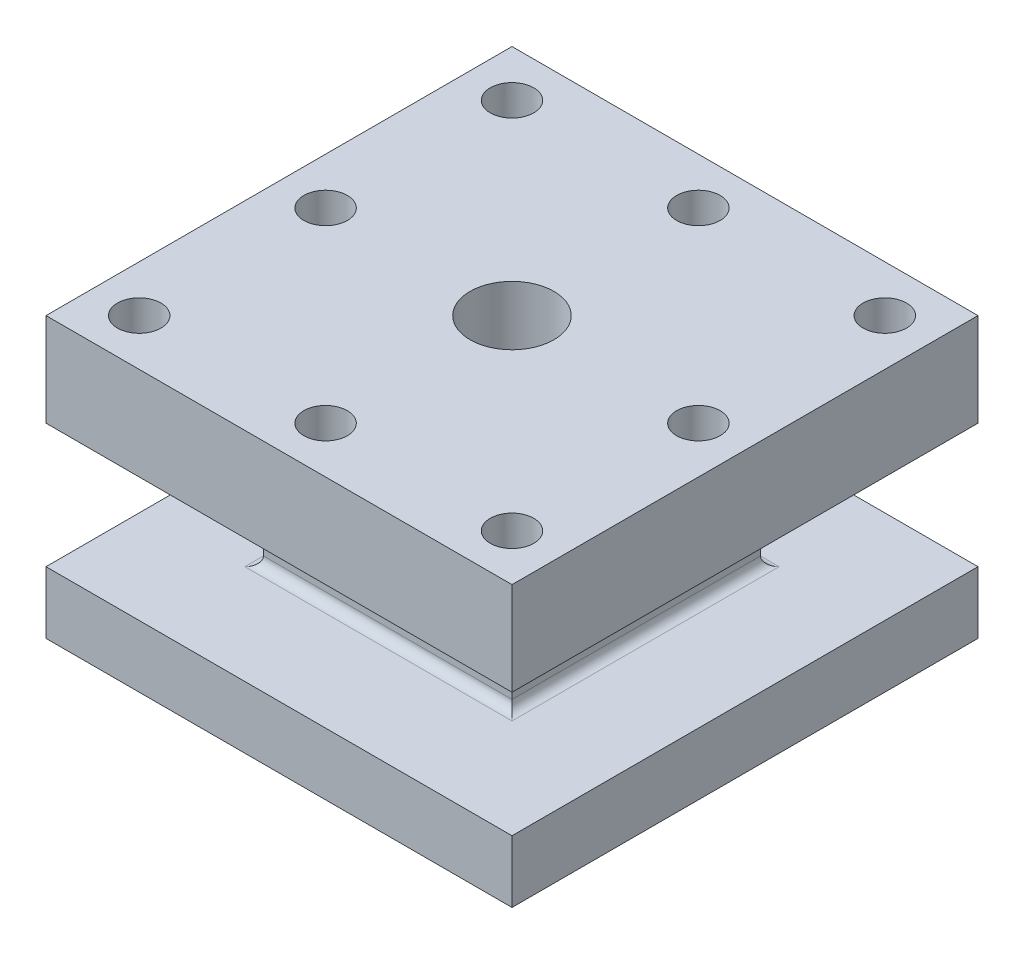
SolidWorks part; units mm, degrees
material "Plain Carbon Steel"
ref_plane "Front Plane" through (0, 0, 0) normal (0, 0, 1) x (1, 0, 0)
ref_plane "Top Plane" through (0, 0, 0) normal (0, 1, 0) x (1, 0, 0)
ref_plane "Right Plane" through (0, 0, 0) normal (1, 0, 0) x (0, 0, -1)
sketch "Sketch1" plane through (0, 0, 0) normal (0, 1, 0) x (1, 0, 0)
  line L1 (-75, -75) -> (75, -75)
  line L2 (-75, -75) -> (-75, 75)
  line L3 (-75, 75) -> (75, 75)
  line L4 (75, -75) -> (75, 75)
  line L5 (-75, -75) -> (75, 75) construction
  line L6 (-75, 75) -> (75, -75) construction
  point P0 (0, 0)
  dimension "D1" = 150
  dimension "D2" = 150
extrude "Boss-Extrude1" add sketch "Sketch1" along normal blind 20
sketch "Sketch2" plane through (0, 20, 0) normal (0, 1, 0) x (1, 0, 0)
  line L1 (-40, -40) -> (40, -40)
  line L2 (-40, -40) -> (-40, 40)
  line L3 (-40, 40) -> (40, 40)
  line L4 (40, -40) -> (40, 40)
  line L5 (-40, -40) -> (40, 40) construction
  line L6 (-40, 40) -> (40, -40) construction
  point P0 (0, 0)
  dimension "D1" = 80
  dimension "D2" = 80
extrude "Boss-Extrude2" add sketch "Sketch2" along normal blind 40
sketch "Sketch3" plane through (0, 60, 0) normal (0, 1, 0) x (1, 0, 0)
  line L1 (-75, -75) -> (75, -75)
  line L2 (-75, -75) -> (-75, 75)
  line L3 (-75, 75) -> (75, 75)
  line L4 (75, -75) -> (75, 75)
  line L5 (-75, -75) -> (75, 75) construction
  line L6 (-75, 75) -> (75, -75) construction
  point P0 (0, 0)
  dimension "D1" = 150
  dimension "D2" = 150
extrude "Boss-Extrude3" add sketch "Sketch3" along normal blind 30
hole_wizard "Hole2" positions "3DSketch4" profile "Sketch6" legacy end condition through all
sketch3d "3DSketch4"
  point P0 (0, 0, 0)
  point P3 (0, 0, 0)
sketch "Sketch6" plane through (0, 0, 0) normal (1, 0, 0) x (0, 0, -1)
  line L0 (0, 0) -> (0, 90)
  line L1 (0, 90) -> (13.5, 90)
  line L2 (13.5, 90) -> (13.5, 10)
  line L3 (13.5, 10) -> (30, 10)
  line L4 (30, 10) -> (30, 0)
  line L5 (30, 0) -> (0, 0)
  line L6 (0, 110) -> (0, -10) construction
  dimension "Diameter" = 27
  dimension "Depth" = 90
  dimension "C-Bore Diameter" = 60
  dimension "C-Bore Depth" = 10
hole_wizard "M16 Tapped Hole1" positions "Sketch9" profile "Sketch10" tap size "M16" standard "DIN" end condition up to next
sketch "Sketch9" plane through (0, 90, 0) normal (0, 1, 0) x (1, 0, 0)
  line L1 (-60, -60) -> (60, -60)
  line L2 (-60, -60) -> (-60, 60)
  line L3 (-60, 60) -> (60, 60)
  line L4 (60, -60) -> (60, 60)
  line L5 (-60, -60) -> (60, 60) construction
  line L6 (-60, 60) -> (60, -60) construction
  point P1 (0, 0)
  point P2 (60, 60)
  point P219 (-60, -60)
  point P220 (-60, 60)
  point P221 (60, -60)
  point P226 (0, 60)
  point P230 (60, 0)
  point P234 (0, -60)
  point P238 (-60, 0)
  point P241 (0, 0)
  point P242 (60, 0)
  dimension "D1" = 120
  dimension "D2" = 120
sketch "Sketch10" plane through (0, 90, 0) normal (1, 0, 0) x (0, 0, 1)
  line L0 (0, 0) -> (0, 90)
  line L1 (0, 90) -> (7, 90)
  line L2 (7, 90) -> (7, 0)
  line L5 (7, 0) -> (0, 0)
  line L11 (0, -6.35) -> (0, 107.95) construction
  dimension "Thru Tap Drill Dia." = 14
  dimension "Thru Tap Drill Depth" = 90
cosmetic thread "Hole Thread1" parameters "D2"=16
cosmetic thread "Hole Thread2" parameters "D2"=16
cosmetic thread "Hole Thread3" parameters "D2"=16
cosmetic thread "Hole Thread4" parameters "D2"=16
cosmetic thread "Hole Thread5" parameters "D2"=16
cosmetic thread "Hole Thread6" parameters "D2"=16
cosmetic thread "Hole Thread7" parameters "D2"=16
cosmetic thread "Hole Thread8" parameters "D2"=16
hole_wizard "Ø10.0 (10) Diameter Hole1" positions "Sketch11" profile "Sketch12" hole size "Ø10.0" standard "DIN"
sketch "Sketch11" plane through (0, 0, 0) normal (0, -1, 0) x (-1, 0, 0)
  line L1 (-60, -60) -> (60, -60)
  line L2 (-60, -60) -> (-60, 60)
  line L3 (-60, 60) -> (60, 60)
  line L4 (60, -60) -> (60, 60)
  line L5 (-60, -60) -> (60, 60) construction
  line L6 (-60, 60) -> (60, -60) construction
  point P1 (0, 0)
  point P216 (0, -60)
  point P218 (60, 0)
  point P220 (-60, 0)
  point P222 (0, 60)
  dimension "D1" = 120
  dimension "D2" = 120
sketch "Sketch12" plane through (0, 0, 0) normal (1, 0, 0) x (0, 0, -1)
  line L0 (0, 0) -> (0, 18)
  line L1 (0, 18) -> (5, 14.9957)
  line L2 (5, 14.9957) -> (5, 0)
  line L5 (5, 0) -> (0, 0)
  line L10 (0, 18) -> (-5, 14.9957) construction
  line L11 (0, -6.35) -> (0, 107.95) construction
  dimension "Hole Dia." = 10
  dimension "Hole Depth" = 18
  dimension "Drill Angle" = 118
fillet "Fillet1" radius 3 4 edges at (0, 20, 40) (40, 20, 0) (0, 20, -40) (-40, 20, 0)
chamfer "Chamfer1" distance 2 angle 45 1 edges at (0, 0, -30)
